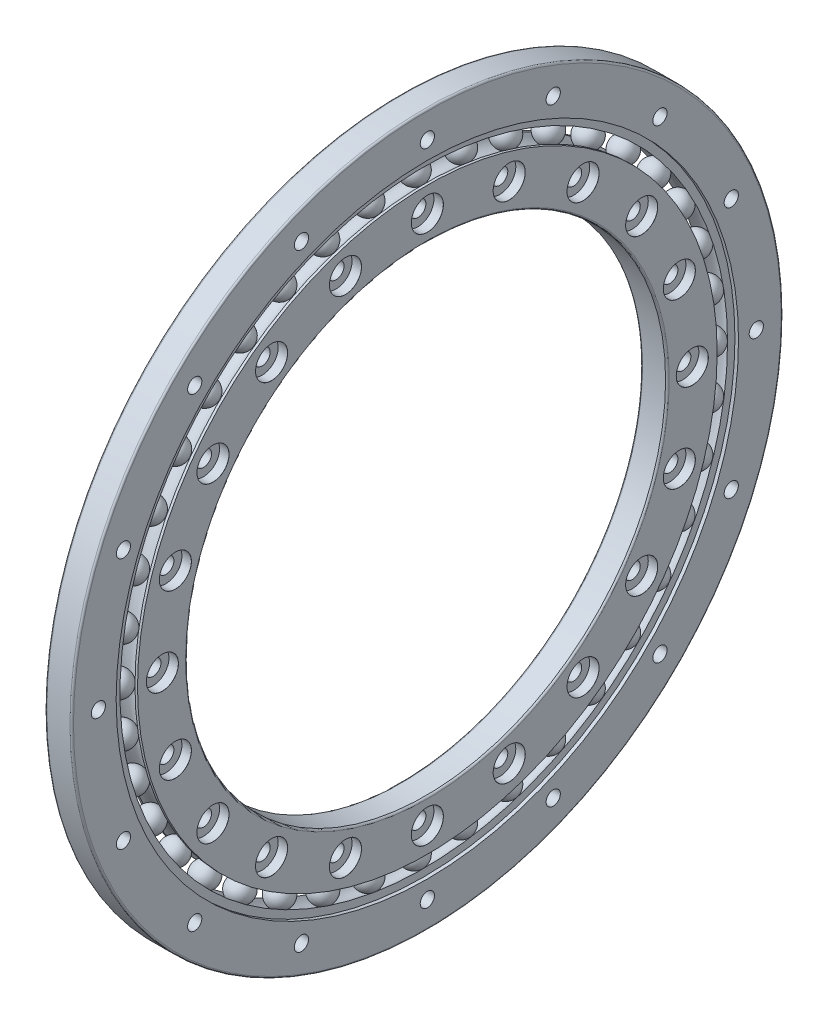
SolidWorks part; units mm, degrees
ref_plane "Front Plane" through (0, 0, 0) normal (0, 0, 1) x (1, 0, 0)
ref_plane "Top Plane" through (0, 0, 0) normal (0, 1, 0) x (1, 0, 0)
ref_plane "Right Plane" through (0, 0, 0) normal (1, 0, 0) x (0, 0, -1)
sketch "Sketch1" plane through (0, 0, 0) normal (0, 0, 1) x (1, 0, 0)
  line L0 (0, 0) -> (0, 185) construction
  line L1 (-4.3728, 170) -> (-4.3728, 163) construction
  line L2 (7.5, 170) -> (-7.5, 170)
  line L3 (7.5, 170) -> (7.5, 200)
  line L4 (7.5, 200) -> (-7.5, 200)
  line L5 (-7.5, 170) -> (-7.5, 200)
  line L6 (7.5, 170) -> (-7.5, 200) construction
  line L7 (7.5, 200) -> (-7.5, 170) construction
  line L8 (7.5, 163) -> (-7.5, 163)
  line L9 (7.5, 163) -> (7.5, 135)
  line L10 (7.5, 135) -> (-7.5, 135)
  line L11 (-7.5, 163) -> (-7.5, 135)
  line L12 (7.5, 163) -> (-7.5, 135) construction
  line L13 (7.5, 135) -> (-7.5, 163) construction
  line L14 (-4.3728, 166.5) -> (0, 166.5) construction
  line L15 (0, 0) -> (-68.3739, 0) construction
  circle A0 centre (0, 166.5) radius 7
  point P7 (0, 149)
  dimension "D6" = 14
  dimension "D1" = 15
  dimension "D2" = 135
  dimension "D3" = 200
  dimension "D4" = 28
  dimension "D5" = 30
revolve "Revolve1" add sketch "Sketch1" angle 360 about L15 region at (0, 185.9722, 0) region at (0, 148.0302, 0)
sketch "Sketch4" plane through (-7.5, 0, 0) normal (-1, 0, 0) x (0, 0, 1)
  circle A1 centre (0, 0) radius 170 construction
  circle A2 centre (0, 0) radius 170
  circle A3 centre (0, 0) radius 175
  dimension "D1" = 5
extrude "Cut-Extrude1" cut sketch "Sketch4" against normal blind 2
mirror "Mirror1" about plane through (0, 0, 0) normal (1, 0, 0) of "Cut-Extrude1"
fillet "Fillet1" radius 1 2 edges at (7.5, 0, -200) (-7.5, 0, -200)
fillet "Fillet2" radius 1 2 edges at (7.5, 0, -135) (-7.5, 0, -135)
sketch "Sketch6" plane through (0, 0, 0) normal (0, 1, 0) x (1, 0, 0)
  line L0 (-6.9, 166.5) -> (6.9, 166.5)
  arc A0 (6.9, 166.5) -> (-6.9, 166.5) centre (0, 166.5) ccw
  dimension "D2" = 13.8
  dimension "D1" = 166.5
revolve "Revolve2" add sketch "Sketch6" angle 360 about L0
ref_axis "Axis1" through (-89.8942, 0, 0) along (1, 0, 0)
pattern_circular "CirPattern1" count 40 over 360 about axis through (-89.8942, 0, 0) along (1, 0, 0) of bodies 105
sketch "Sketch7" plane through (7.5, 0, 0) normal (1, 0, 0) x (0, 0, -1)
  line L0 (0, 163) -> (0, 135) construction
  circle A0 centre (0, 0) radius 135 construction
  circle A1 centre (0, 0) radius 163 construction
  circle A2 centre (0, 0) radius 135 construction
  circle A3 centre (0, 0) radius 163 construction
  point P8 (0, 149)
hole_wizard "CBORE for M8 Hex Head Bolt1" positions "3DSketch3" profile "Sketch8" counterbore size "M8" standard "ISO" end condition through all
sketch3d "3DSketch3"
  point P0 (7.5, 149, 0)
sketch "Sketch8" plane through (7.5, 149, 0) normal (0, 1, 0) x (0, 0, -1)
  line L0 (0, 0) -> (0, 15)
  line L1 (0, 15) -> (4.5, 15)
  line L3 (4.5, 15) -> (4.5, 5.3)
  line L4 (9.0055, 5.3) -> (4.5, 5.3)
  line L5 (9.0055, 5.3) -> (9.0055, 0.025)
  line L6 (9.0055, 0.025) -> (9.0305, 0)
  line L7 (9.0305, 0) -> (0, 0)
  line L8 (-9.0055, 0.025) -> (-9.0305, 0) construction
  line L11 (0, -6.35) -> (0, 107.95) construction
  dimension "Thru Hole Dia." = 9
  dimension "Thru Hole Depth" = 15
  dimension "C'Bore Dia." = 18.011
  dimension "C'Bore Depth" = 5.3
  dimension "Near C'Sink Dia." = 18.061
  dimension "Near C'Sink Angle" = 90
pattern_circular "CirPattern2" count 20 over 360 about axis through (-89.8942, 0, 0) along (1, 0, 0) of "CBORE for M8 Hex Head Bolt1"
sketch "Sketch9" plane through (7.5, 0, 0) normal (1, 0, 0) x (0, 0, -1)
  point P7 (0, 185)
  dimension "D1" = 185
hole_wizard "Ø8.0mm Dowel Hole1" positions "3DSketch7" profile "Sketch12" hole size "Ø8.0" standard "ISO" end condition through all
sketch3d "3DSketch7"
  point P0 (7.5, 185, 0)
sketch "Sketch12" plane through (7.5, 185, 0) normal (0, 1, 0) x (0, 0, -1)
  line L0 (0, 0) -> (0, 15)
  line L1 (0, 15) -> (4, 15)
  line L2 (4, 15) -> (4, 0)
  line L5 (4, 0) -> (0, 0)
  line L11 (0, -6.35) -> (0, 107.95) construction
  dimension "Thru Hole Dia." = 8
  dimension "Thru Hole Depth" = 15
pattern_circular "CirPattern3" count 16 over 360 about axis through (-89.8942, 0, 0) along (1, 0, 0) of "Ø8.0mm Dowel Hole1"
